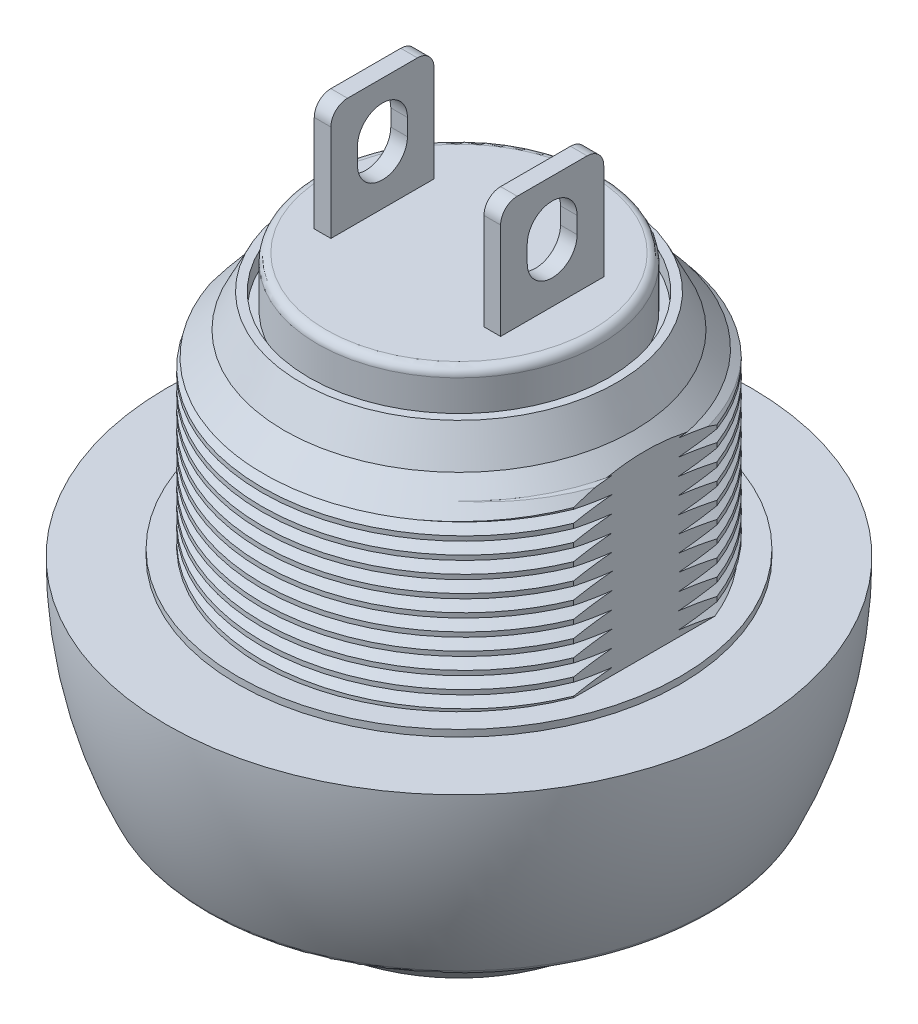
SolidWorks part; units mm, degrees
ref_plane "Front Plane" through (0, 0, 0) normal (0, 0, 1) x (1, 0, 0)
ref_plane "Top Plane" through (0, 0, 0) normal (0, 1, 0) x (1, 0, 0)
ref_plane "Right Plane" through (0, 0, 0) normal (1, 0, 0) x (0, 0, -1)
sketch "Sketch1" plane through (0, 0, 0) normal (0, 1, 0) x (1, 0, 0)
  circle A0 centre (0, 0) radius 6
  dimension "D1" = 12
extrude "Boss-Extrude1" add sketch "Sketch1" along normal blind 5.7
sketch "Sketch4" plane through (0, 5.7, 0) normal (0, 1, 0) x (1, 0, 0)
  circle A0 centre (0, 0) radius 6
chamfer "Chamfer1" distance 0.75 angle 45 1 edges at (0, 5.7, 6)
curve "Helix/Spiral1" pitch 0.5 height 5.7 radius 6 left hand yes centre (0, 5.7, 0) axis (0, -1, 0) start towards (1, 0, 0)
sketch "Sketch8" plane through (0, 5.7, 0) normal (0, 1, 0) x (1, 0, 0)
  circle A0 centre (0, 0) radius 5.25
extrude "Boss-Extrude2" add sketch "Sketch8" along normal blind 1
sketch "Sketch9" plane through (0, 0, 0) normal (1, 0, 0) x (0, 0, -1)
  line L0 (5.25, 6.7) -> (4.75, 6.7)
  line L3 (5.25, 6.7) -> (5.25, 5.7)
  line L5 (5.25, 5.7) -> (4.75, 6.7)
ref_axis "Axis1" through (0, 0, 0) along (0, 1, 0)
revolve "Cut-Revolve1" cut sketch "Sketch9" angle 360 about axis through (0, 0, 0) along (0, 1, 0) region at (0, 6.3667, -5.0833)
sketch "Sketch10" plane through (0, 6.7, 0) normal (0, 1, 0) x (1, 0, 0)
  circle A0 centre (0, 0) radius 4.5
  dimension "D1" = 9
extrude "Cut-Extrude1" cut sketch "Sketch10" against normal blind 0.5
sketch "Sketch11" plane through (0, 6.2, 0) normal (0, 1, 0) x (1, 0, 0)
  circle A0 centre (0, 0) radius 4.25
  dimension "D1" = 8.5
extrude "Boss-Extrude3" add sketch "Sketch11" along normal blind 1.5
fillet "Fillet1" radius 0.25 1 edges at (0, 7.7, 4.25)
sketch "Sketch12" plane through (0, 7.7, 0) normal (0, 1, 0) x (1, 0, 0)
  line L0 (-5.6, 5.5) -> (-7.6, 5.5)
  line L2 (-5.6, 5.5) -> (-5.6, -5.5)
  line L4 (5.6, 5.5) -> (5.6, -5.5)
  line L7 (-7.6, 5.5) -> (-7.6, -5.5)
  line L8 (-7.6, -5.5) -> (-5.6, -5.5)
  line L9 (5.6, 5.5) -> (7.6, 5.5)
  line L10 (7.6, 5.5) -> (7.6, -5.5)
  line L11 (7.6, -5.5) -> (5.6, -5.5)
  point P0 (0, 0)
  dimension "D1" = 5.6
  dimension "D2" = 11
  dimension "D3" = 11
  dimension "D4" = 2
  dimension "D5" = 2
  dimension "D6" = 5.6
extrude "Cut-Extrude2" cut sketch "Sketch12" against normal up to surface (7.7 mm away) up to face at (0, 0, 6)
sketch "Sketch13" plane through (0, 0, 0) normal (0, 0, 1) x (1, 0, 0)
  line L1 (5.6868, 5.6982) -> (6.1391, 5.4315)
  line L2 (6.1391, 5.4315) -> (6.1439, 5.9566)
  line L3 (6.1439, 5.9566) -> (5.6868, 5.6982)
  circle A0 centre (5.9899, 5.6954) radius 0.1516 construction
  spline S0 degree 3 poles (6, 5.7) (6, 5.6896) (5.6862, 5.6687) (4.3461, 5.6374) (2.3414, 5.606) (-0.0213, 5.5747) (-2.3807, 5.5434) (-4.3761, 5.5121) (-5.7024, 5.4808) (-6.1568, 5.4495) (-5.6698, 5.4181) (-4.3158, 5.3868) (-2.302, 5.3555) (0.0638, 5.3242) (2.4198, 5.2929) (4.4059, 5.2615) (5.7183, 5.2302) (6.1563, 5.1989) (5.6531, 5.1676) (4.2854, 5.1363) (2.2626, 5.1049) (-0.1063, 5.0736) (-2.4588, 5.0423) (-4.4355, 5.011) (-5.7339, 4.9797) (-6.1556, 4.9484) (-5.6361, 4.917) (-4.2548, 4.8857) (-2.223, 4.8544) (0.1488, 4.8231) (2.4978, 4.7918) (4.4648, 4.7604) (5.7492, 4.7291) (6.1546, 4.6978) (5.6188, 4.6665) (4.224, 4.6352) (2.1833, 4.6038) (-0.1913, 4.5725) (-2.5366, 4.5412) (-4.494, 4.5099) (-5.7643, 4.4786) (-6.1532, 4.4473) (-5.6013, 4.4159) (-4.1929, 4.3846) (-2.1435, 4.3533) (0.2338, 4.322) (2.5752, 4.2907) (4.523, 4.2593) (5.7791, 4.228) (6.1516, 4.1967) (5.5835, 4.1654) (4.1617, 4.1341) (2.1036, 4.1027) (-0.2762, 4.0714) (-2.6138, 4.0401) (-4.5517, 4.0088) (-5.7936, 3.9775) (-6.1497, 3.9462) (-5.5655, 3.9148) (-4.1303, 3.8835) (-2.0636, 3.8522) (0.3187, 3.8209) (2.6522, 3.7896) (4.5802, 3.7582) (5.8079, 3.7269) (6.1475, 3.6956) (5.5472, 3.6643) (4.0987, 3.633) (2.0235, 3.6016) (-0.3611, 3.5703) (-2.6905, 3.539) (-4.6085, 3.5077) (-5.8218, 3.4764) (-6.145, 3.4451) (-5.5286, 3.4137) (-4.0668, 3.3824) (-1.9833, 3.3511) (0.4036, 3.3198) (2.7287, 3.2885) (4.6366, 3.2571) (5.8355, 3.2258) (6.1422, 3.1945) (5.5098, 3.1632) (4.0348, 3.1319) (1.943, 3.1005) (-0.446, 3.0692) (-2.7667, 3.0379) (-4.6644, 3.0066) (-5.849, 2.9753) (-6.1392, 2.944) (-5.4907, 2.9126) (-4.0026, 2.8813) (-1.9026, 2.85) (0.4884, 2.8187) (2.8046, 2.7874) (4.6921, 2.756) (5.8621, 2.7247) (6.1358, 2.6934) (5.4713, 2.6621) (3.9702, 2.6308) (1.8621, 2.5995) (-0.5307, 2.5681) (-2.8424, 2.5368) (-4.7195, 2.5055) (-5.875, 2.4742) (-6.1321, 2.4429) (-5.4517, 2.4115) (-3.9376, 2.3802) (-1.8215, 2.3489) (0.5731, 2.3176) (2.8801, 2.2863) (4.7467, 2.2549) (5.8875, 2.2236) (6.1282, 2.1923) (5.4318, 2.161) (3.9049, 2.1297) (1.7809, 2.0984) (-0.6154, 2.067) (-2.9176, 2.0357) (-4.7736, 2.0044) (-5.8998, 1.9731) (-6.1239, 1.9418) (-5.4116, 1.9104) (-3.8719, 1.8791) (-1.7402, 1.8478) (0.6577, 1.8165) (2.9549, 1.7852) (4.8004, 1.7538) (5.9118, 1.7225) (6.1194, 1.6912) (5.3912, 1.6599) (3.8388, 1.6286) (1.6993, 1.5973) (-0.6999, 1.5659) (-2.9922, 1.5346) (-4.8269, 1.5033) (-5.9236, 1.472) (-6.1145, 1.4407) (-5.3706, 1.4093) (-3.8054, 1.378) (-1.6584, 1.3467) (0.7421, 1.3154) (3.0292, 1.2841) (4.8532, 1.2527) (5.935, 1.2214) (6.1094, 1.1901) (5.3497, 1.1588) (3.7719, 1.1275) (1.6175, 1.0962) (-0.7843, 1.0648) (-3.0662, 1.0335) (-4.8792, 1.0022) (-5.9462, 0.9709) (-6.104, 0.9396) (-5.3285, 0.9082) (-3.7382, 0.8769) (-1.5764, 0.8456) (0.8265, 0.8143) (3.103, 0.783) (4.905, 0.7516) (5.9571, 0.7203) (6.0983, 0.689) (5.3071, 0.6577) (3.7044, 0.6264) (1.5353, 0.5951) (-0.8686, 0.5637) (-3.1396, 0.5324) (-4.9306, 0.5011) (-5.9677, 0.4698) (-6.0923, 0.4385) (-5.2854, 0.4071) (-3.6703, 0.3758) (-1.4941, 0.3445) (0.9106, 0.3132) (3.1761, 0.2819) (4.9559, 0.2505) (5.978, 0.2192) (6.086, 0.1879) (5.2635, 0.1566) (3.6361, 0.1253) (1.4529, 0.094) (-0.953, 0.0626) (-3.2111, 0.0313) (-4.3944, 0.0104) (-4.8541, 0) knots 0 0 0 0 0.005495 0.010989 0.016484 0.021978 0.027473 0.032967 0.038462 0.043956 0.049451 0.054945 0.06044 0.065934 0.071429 0.076923 0.082418 0.087912 0.093407 0.098901 0.104396 0.10989 0.115385 0.120879 0.126374 0.131868 0.137363 0.142857 0.148352 0.153846 0.159341 0.164835 0.17033 0.175824 0.181319 0.186813 0.192308 0.197802 0.203297 0.208791 0.214286 0.21978 0.225275 0.230769 0.236264 0.241758 0.247253 0.252747 0.258242 0.263736 0.269231 0.274725 0.28022 0.285714 0.291209 0.296703 0.302198 0.307692 0.313187 0.318681 0.324176 0.32967 0.335165 0.340659 0.346154 0.351648 0.357143 0.362637 0.368132 0.373626 0.379121 0.384615 0.39011 0.395604 0.401099 0.406593 0.412088 0.417582 0.423077 0.428571 0.434066 0.43956 0.445055 0.450549 0.456044 0.461538 0.467033 0.472527 0.478022 0.483516 0.489011 0.494505 0.5 0.505495 0.510989 0.516484 0.521978 0.527473 0.532967 0.538462 0.543956 0.549451 0.554945 0.56044 0.565934 0.571429 0.576923 0.582418 0.587912 0.593407 0.598901 0.604396 0.60989 0.615385 0.620879 0.626374 0.631868 0.637363 0.642857 0.648352 0.653846 0.659341 0.664835 0.67033 0.675824 0.681319 0.686813 0.692308 0.697802 0.703297 0.708791 0.714286 0.71978 0.725275 0.730769 0.736264 0.741758 0.747253 0.752747 0.758242 0.763736 0.769231 0.774725 0.78022 0.785714 0.791209 0.796703 0.802198 0.807692 0.813187 0.818681 0.824176 0.82967 0.835165 0.840659 0.846154 0.851648 0.857143 0.862637 0.868132 0.873626 0.879121 0.884615 0.89011 0.895604 0.901099 0.906593 0.912088 0.917582 0.923077 0.928571 0.934066 0.93956 0.945055 0.950549 0.956044 0.961538 0.967033 0.972527 0.978022 0.983516 0.989011 0.994505 1 1 1 1 construction
sweep "Cut-Sweep7" cut profiles "Sketch13" path "Helix/Spiral1" align with end faces yes
sketch "Sketch14" plane through (0, 7.7, 0) normal (0, 1, 0) x (1, 0, 0)
  line L0 (-2.3, 1.55) -> (-2.3, -1.55)
  line L1 (-2.8, 1.55) -> (-2.3, 1.55)
  line L2 (-2.8, 1.55) -> (-2.8, -1.55)
  line L3 (-2.8, -1.55) -> (-2.3, -1.55)
  line L4 (2.8, 1.55) -> (2.8, -1.55)
  line L5 (-2.8, 1.55) -> (2.8, -1.55) construction
  line L6 (-2.8, -1.55) -> (2.8, 1.55) construction
  line L7 (2.3, 1.55) -> (2.3, -1.55)
  line L8 (2.3, 1.55) -> (2.8, 1.55)
  line L9 (2.3, -1.55) -> (2.8, -1.55)
  point P0 (0, 0)
  dimension "D1" = 5.6
  dimension "D2" = 3.1
  dimension "D3" = 0.5
  dimension "D4" = 0.5
extrude "Boss-Extrude4" add sketch "Sketch14" along normal blind 3.4
sketch "Sketch15" plane through (-2.8, 0, 0) normal (-1, 0, 0) x (0, 0, 1)
  line L0 (-1.55, 7.7) -> (1.55, 7.7) construction
  line L1 (0.75, 9.7) -> (0.75, 9.2)
  line L2 (-0.75, 9.7) -> (-0.75, 9.2)
  arc A0 (0.75, 9.7) -> (-0.75, 9.7) centre (0, 9.7) ccw
  arc A1 (-0.75, 9.2) -> (0.75, 9.2) centre (0, 9.2) ccw
  dimension "D1" = 0.5
  dimension "D2" = 1.5
extrude "Cut-Extrude3" cut sketch "Sketch15" against normal up to surface (5.6 mm away) up to face at (2.8, 9.4, 0)
fillet "Fillet2" radius 0.5 4 edges at (2.55, 11.1, 1.55) (2.55, 11.1, -1.55) (-2.55, 11.1, 1.55) (-2.55, 11.1, -1.55)
sketch "Sketch16" plane through (0, 0, 0) normal (0, -1, 0) x (1, 0, 0)
  circle A0 centre (0, 0) radius 6.65
extrude "Boss-Extrude5" add sketch "Sketch16" along normal blind 0.2
sketch "Sketch17" plane through (0, -0.2, 0) normal (0, -1, 0) x (1, 0, 0)
  circle A0 centre (0, 0) radius 8.775
  dimension "D1" = 17.55
extrude "Boss-Extrude6" add sketch "Sketch17" along normal blind 5.6
sketch "Sketch18" plane through (0, -5.8, 0) normal (0, -1, 0) x (-1, 0, 0)
  circle A0 centre (0, 0) radius 7.5 construction
  circle A1 centre (0, 0) radius 6.25
  dimension "D1" = 15
  dimension "D2" = 12.5
sketch "Sketch19" plane through (0, 0, 0) normal (0, 0, 1) x (1, 0, 0)
  line L2 (-7.5, -5.8) -> (7.5, -5.8) construction
  line L3 (-7.5, -5.8) -> (-8.775, -5.8)
  line L4 (-8.775, -5.8) -> (-8.775, -0.2)
  arc A0 (-8.775, -0.2) -> (-7.5, -5.8) centre (4.1605, -0.2) ccw
revolve "Cut-Revolve2" cut sketch "Sketch19" angle 360 about axis through (0, 0, 0) along (0, 1, 0)
extrude "Cut-Extrude4" cut sketch "Sketch18" against normal blind 3
fillet "Fillet3" radius 0.3 1 edges at (0, -5.8, -7.5)
sketch "Sketch20" plane through (0, -2.8, 0) normal (0, -1, 0) x (1, 0, 0)
  circle A0 centre (0, 0) radius 6.05
  dimension "D1" = 12.1
extrude "Boss-Extrude7" add sketch "Sketch20" along normal blind 6
sketch "Sketch22" plane through (0, -8.8, 0) normal (0, -1, 0) x (1, 0, 0)
  circle A0 centre (0, 0) radius 3
sketch "Sketch23" plane through (0, 0, 0) normal (0, 0, 1) x (1, 0, 0)
  line L1 (6.05, -8.8) -> (6.05, -2.8) construction
  line L2 (-3, -8.8) -> (3, -8.8) construction
  line L3 (-6.05, -8.8) -> (6.05, -8.8) construction
  line L4 (6.05, -6.05) -> (6.05, -8.8)
  line L5 (6.05, -8.8) -> (3, -8.8)
  arc A1 (6.05, -6.05) -> (3, -8.8) centre (1.266, -3.8104) cw
  dimension "D1" = 2.75
revolve "Cut-Revolve3" cut sketch "Sketch23" angle 360 about axis through (0, 0, 0) along (0, 1, 0)
fillet "Fillet4" radius 0.1 2 edges at (0, -8.8, -3) (0, -6.05, -6.05)
